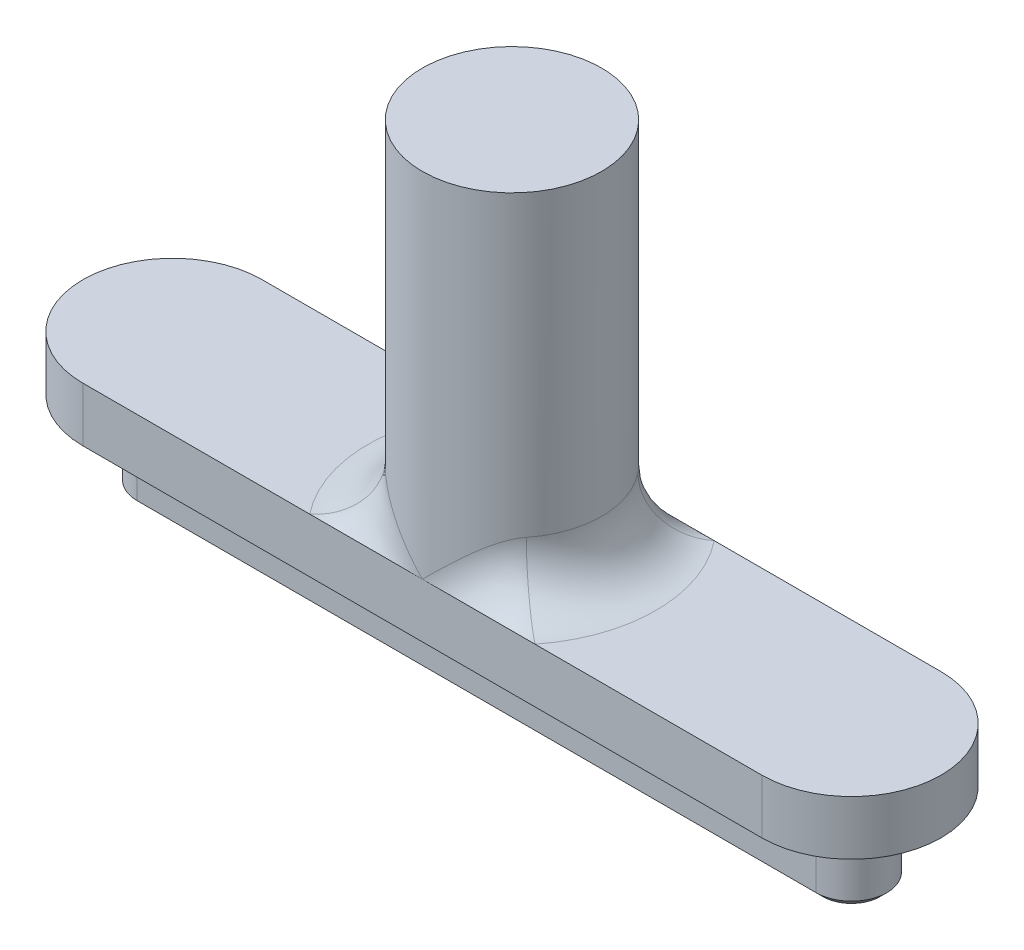
SolidWorks part; units mm, degrees
ref_plane "Front Plane" through (0, 0, 0) normal (0, 0, 1) x (1, 0, 0)
ref_plane "Top Plane" through (0, 0, 0) normal (0, 1, 0) x (1, 0, 0)
ref_plane "Right Plane" through (0, 0, 0) normal (1, 0, 0) x (0, 0, -1)
sketch "Sketch1" plane through (0, 0, 0) normal (0, 1, 0) x (1, 0, 0)
  line L0 (-12.5, 0) -> (12.5, 0) construction
  line L1 (-12.5, 1.5) -> (12.5, 1.5)
  line L2 (-12.5, -1.5) -> (12.5, -1.5)
  line L3 (-12.5, 1.3) -> (12.5, 1.3)
  line L4 (-12.5, -1.3) -> (12.5, -1.3)
  arc A0 (-12.5, 1.5) -> (-12.5, -1.5) centre (-12.5, 0) ccw
  arc A1 (12.5, -1.5) -> (12.5, 1.5) centre (12.5, 0) ccw
  arc A2 (12.5, -1.3) -> (12.5, 1.3) centre (12.5, 0) ccw
  arc A3 (-12.5, 1.3) -> (-12.5, -1.3) centre (-12.5, 0) ccw
  point P2 (0, 0)
  dimension "D1" = 25
  dimension "D2" = 3
  dimension "D3" = 0.2
extrude "Boss-Extrude1" add sketch "Sketch1" along normal blind 3 contours L3 A2 L4 A3
sketch "Sketch2" plane through (0, 3, 0) normal (0, 1, 0) x (1, 0, 0)
  line L4 (-12.5, -3.3) -> (12.5, -3.3)
  line L5 (12.5, 3.3) -> (-12.5, 3.3)
  line L6 (-12.5, -3.3) -> (12.5, -3.3)
  line L7 (12.5, 3.3) -> (-12.5, 3.3)
  arc A4 (-12.5, 3.3) -> (-12.5, -3.3) centre (-12.5, 0) ccw
  arc A5 (12.5, -3.3) -> (12.5, 3.3) centre (12.5, 0) ccw
  arc A6 (-12.5, 3.3) -> (-12.5, -3.3) centre (-12.5, 0) ccw
  arc A7 (12.5, -3.3) -> (12.5, 3.3) centre (12.5, 0) ccw
  dimension "D1" = 2
extrude "Boss-Extrude2" add sketch "Sketch2" along normal blind 2
ref_plane "Plane1" through (0, 10, 0) normal (0, 1, 0) x (1, 0, 0)
chamfer "Chamfer1" distance 0.25 angle 45 4 edges at (13.8, 0, 0) (0, 0, -1.3) (0, 0, 1.3) (-13.8, 0, 0)
sketch "Sketch3" plane through (0, 5, 0) normal (0, 1, 0) x (1, 0, 0)
  circle A0 centre (0, 0) radius 3.3
  dimension "D1" = 6.6
extrude "Boss-Extrude3" add sketch "Sketch3" along normal blind 13
fillet "Fillet1" radius 2 2 edges at (3.3, 5, 0) (-3.3, 5, 0)
